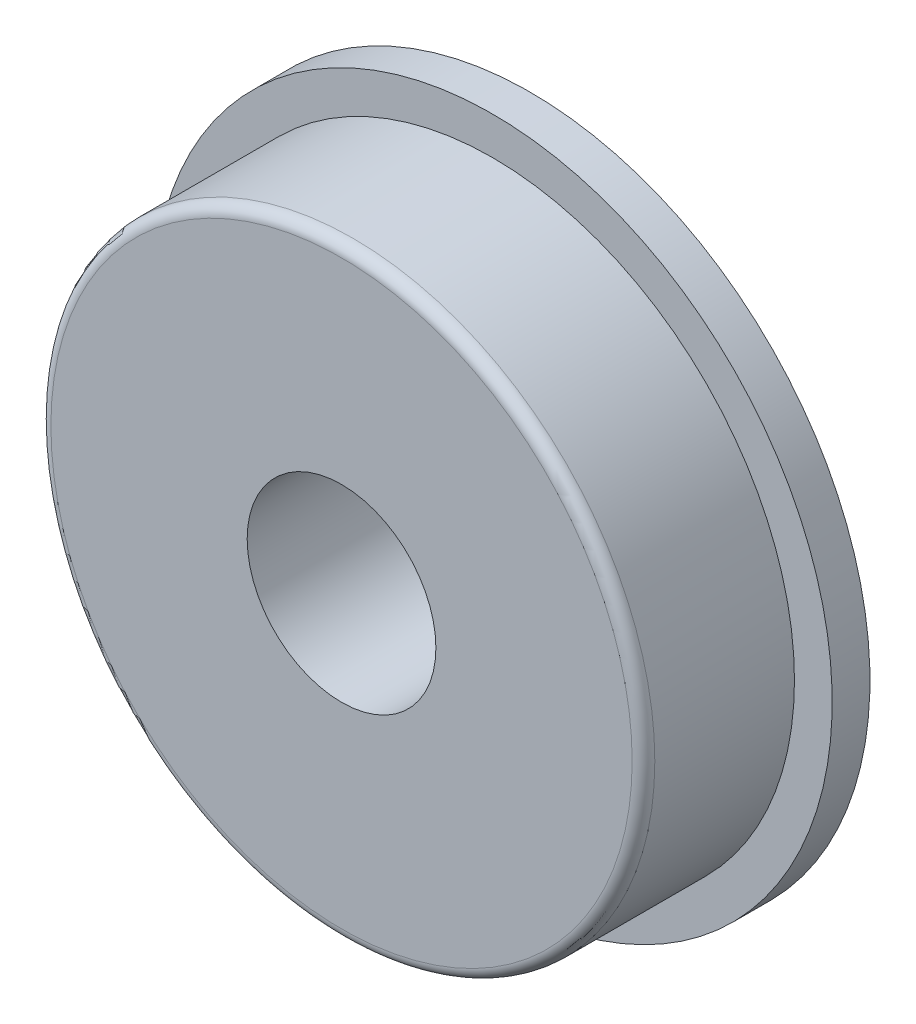
SolidWorks part; units mm, degrees
ref_plane "Alzado" through (0, 0, 0) normal (0, 0, 1) x (1, 0, 0)
ref_plane "Planta" through (0, 0, 0) normal (0, 1, 0) x (1, 0, 0)
ref_plane "Vista lateral" through (0, 0, 0) normal (1, 0, 0) x (0, 0, -1)
sketch "Croquis1" plane through (0, 0, 0) normal (0, 0, 1) x (1, 0, 0)
  circle A0 centre (0, 0) radius 2.5
  circle A1 centre (0, 0) radius 8
  dimension "D1" = 5
  dimension "D2" = 16
extrude "Saliente-Extruir1" add sketch "Croquis1" along normal blind 4
sketch "Croquis2" plane through (0, 0, 0) normal (0, 0, -1) x (-1, 0, 0)
  circle A0 centre (0, 0) radius 9
  circle A3 centre (0, 0) radius 2.5 construction
  circle A4 centre (0, 0) radius 2.5
  dimension "D1" = 18
extrude "Saliente-Extruir2" add sketch "Croquis2" along normal blind 1
fillet "Redondeo1" radius 0.3 1 edges at (8, 0, 4)
